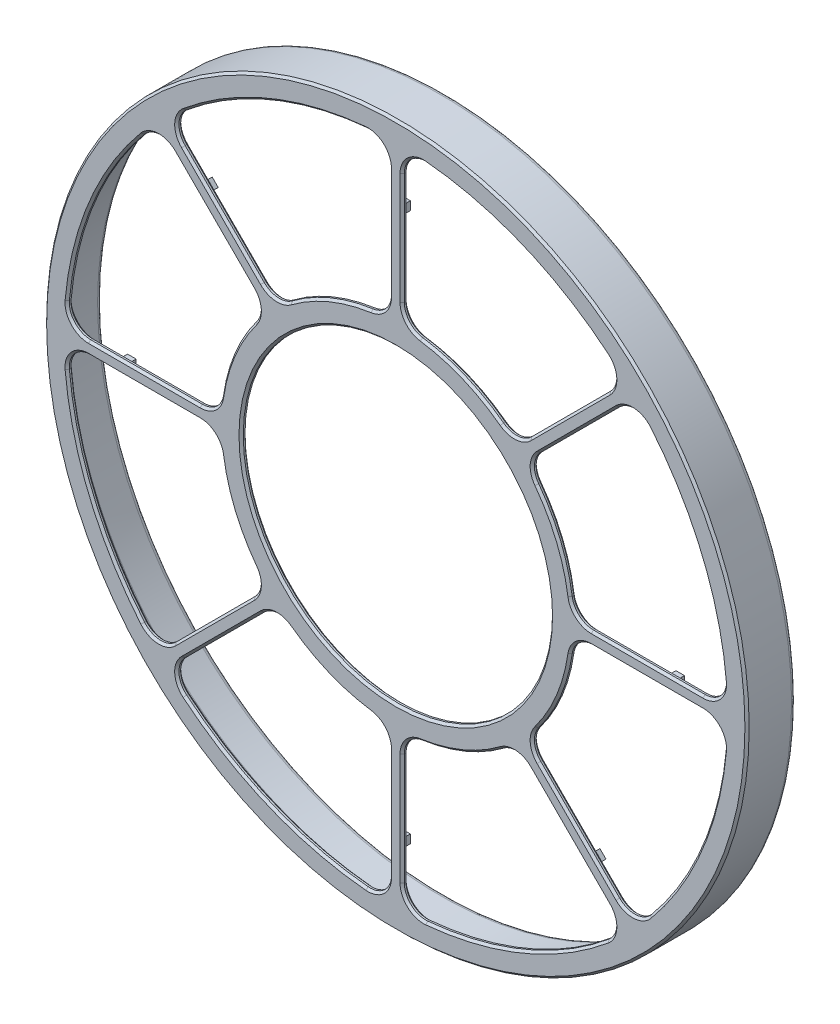
SolidWorks part; units mm, degrees
ref_plane "Front" through (0, 0, 0) normal (0, 0, 1) x (1, 0, 0)
ref_plane "Top" through (0, 0, 0) normal (0, 1, 0) x (1, 0, 0)
ref_plane "Right" through (0, 0, 0) normal (1, 0, 0) x (0, 0, -1)
other "Configuration Table"
sketch "Sketch1" plane through (0, 0, 0) normal (0, 0, 1) x (1, 0, 0)
  line L0 (0, 0) -> (0, 97.79) construction
  line L1 (38.2313, 35.5372) -> (70.4819, 67.7878)
  line L3 (-1.905, 52.1622) -> (-1.905, 97.7714)
  line L5 (1.905, 52.1622) -> (1.905, 97.7714)
  line L6 (35.5372, 38.2313) -> (67.7878, 70.4819)
  line L7 (52.1622, -1.905) -> (97.7714, -1.905)
  line L8 (52.1622, 1.905) -> (97.7714, 1.905)
  line L9 (35.5372, -38.2313) -> (67.7878, -70.4819)
  line L10 (38.2313, -35.5372) -> (70.4819, -67.7878)
  line L11 (-1.905, -52.1622) -> (-1.905, -97.7714)
  line L12 (1.905, -52.1622) -> (1.905, -97.7714)
  line L13 (-38.2313, -35.5372) -> (-70.4819, -67.7878)
  line L14 (-35.5372, -38.2313) -> (-67.7878, -70.4819)
  line L15 (-52.1622, 1.905) -> (-97.7714, 1.905)
  line L16 (-52.1622, -1.905) -> (-97.7714, -1.905)
  line L17 (-35.5372, 38.2313) -> (-67.7878, 70.4819)
  line L18 (-38.2313, 35.5372) -> (-70.4819, 67.7878)
  circle A0 centre (0, 0) radius 45.847
  circle A1 centre (0, 0) radius 104.14
  circle A2 centre (0, 0) radius 97.79
  circle A3 centre (0, 0) radius 52.197
  point P16 (0, 48.0198)
  point P47 (0, 0)
  dimension "D1" = 91.694
  dimension "D2" = 208.28
  dimension "D7" = 3.81
  dimension "D8" = 1.905
  dimension "D3" = 6.35
  dimension "D4" = 6.35
  dimension "D9" = 8
extrude "Boss-Extrude5" add sketch "Sketch1" along normal blind 1.778
fillet "Fillet1" radius 6.35 32 edges at (35.5372, 38.2313, 0.889) (67.7878, 70.4819, 0.889) (1.905, 97.7714, 0.889) (97.7714, 1.905, 0.889) (70.4819, 67.7878, 0.889) (38.2313, 35.5372, 0.889) (52.1622, 1.905, 0.889) (97.7714, -1.905, 0.889) (52.1622, -1.905, 0.889) (38.2313, -35.5372, 0.889) (70.4819, -67.7878, 0.889) (1.905, -52.1622, 0.889) (1.905, -97.7714, 0.889) (67.7878, -70.4819, 0.889) (35.5372, -38.2313, 0.889) (-1.905, -52.1622, 0.889) (-1.905, -97.7714, 0.889) (-35.5372, -38.2313, 0.889) (-67.7878, -70.4819, 0.889) (-38.2313, -35.5372, 0.889) (-70.4819, -67.7878, 0.889) (-52.1622, -1.905, 0.889) (-97.7714, -1.905, 0.889) (-97.7714, 1.905, 0.889) (-52.1622, 1.905, 0.889) (-70.4819, 67.7878, 0.889) (-38.2313, 35.5372, 0.889) (-1.905, 97.7714, 0.889) (-67.7878, 70.4819, 0.889) (1.905, 52.1622, 0.889) (-35.5372, 38.2313, 0.889) (-1.905, 52.1622, 0.889)
sketch "Sketch2" plane through (0, 0, 0) normal (0, 0, -1) x (-1, 0, 0)
  circle A0 centre (0, 0) radius 104.14
  circle A1 centre (0, 0) radius 101.6
  circle A3 centre (0, 0) radius 104.14 construction
  dimension "D1" = 2.54
extrude "Boss-Extrude6" add sketch "Sketch2" along normal blind 12.7 contours A0 | A1
fillet "Fillet2" radius 2.54 1 edges at (-101.6, 0, 0)
chamfer "Chamfer2" distance 0.635 angle 45 131 edges at (-40.4884, -35.597, 1.778) (-40.4884, -35.597, 0) (-54.0366, -51.3426, 1.778) (-54.0366, -51.3426, 0) (-70.5179, -64.9002, 1.778) (-70.5179, -64.9002, 0) (-90.3462, -37.4226, 1.778) (-90.3462, -37.4226, 0) (-95.755, -3.9723, 1.778) (-95.755, -3.9723, 0) (-74.5144, -1.905, 0) (-74.5144, -1.905, 1.778) (-53.8006, -3.4588, 1.778) (-53.8006, -3.4588, 0) (-48.2237, -19.9749, 1.778) (-48.2237, -19.9749, 0) (-3.4588, -53.8006, 1.778) (-3.4588, -53.8006, 0) (-1.905, -74.5144, 1.778) (-1.905, -74.5144, 0) (-3.9723, -95.755, 1.778) (-3.9723, -95.755, 0) (-37.4226, -90.3462, 1.778) (-37.4226, -90.3462, 0) (-64.9002, -70.5179, 1.778) (-64.9002, -70.5179, 0) (-51.3426, -54.0366, 0) (-51.3426, -54.0366, 1.778) (-35.597, -40.4884, 1.778) (-35.597, -40.4884, 0) (-19.9749, -48.2237, 1.778) (-19.9749, -48.2237, 0) (35.597, -40.4884, 1.778) (35.597, -40.4884, 0) (51.3426, -54.0366, 0) (51.3426, -54.0366, 1.778) (64.9002, -70.5179, 1.778) (64.9002, -70.5179, 0) (37.4226, -90.3462, 1.778) (37.4226, -90.3462, 0) (3.9723, -95.755, 1.778) (3.9723, -95.755, 0) (1.905, -74.5144, 0) (1.905, -74.5144, 1.778) (3.4588, -53.8006, 1.778) (3.4588, -53.8006, 0) (19.9749, -48.2237, 1.778) (19.9749, -48.2237, 0) (53.8006, -3.4588, 1.778) (53.8006, -3.4588, 0) (74.5144, -1.905, 0) (74.5144, -1.905, 1.778) (95.755, -3.9723, 1.778) (95.755, -3.9723, 0) (90.3462, -37.4226, 1.778) (90.3462, -37.4226, 0) (70.5179, -64.9002, 1.778) (70.5179, -64.9002, 0) (54.0366, -51.3426, 0) (54.0366, -51.3426, 1.778) (40.4884, -35.597, 1.778) (40.4884, -35.597, 0) (48.2237, -19.9749, 1.778) (48.2237, -19.9749, 0) (40.4884, 35.597, 1.778) (40.4884, 35.597, 0) (54.0366, 51.3426, 0) (54.0366, 51.3426, 1.778) (70.5179, 64.9002, 1.778) (70.5179, 64.9002, 0) (90.3462, 37.4226, 1.778) (90.3462, 37.4226, 0) (95.755, 3.9723, 1.778) (95.755, 3.9723, 0) (74.5144, 1.905, 1.778) (74.5144, 1.905, 0) (53.8006, 3.4588, 1.778) (53.8006, 3.4588, 0) (48.2237, 19.9749, 1.778) (48.2237, 19.9749, 0) (3.4588, 53.8006, 1.778) (3.4588, 53.8006, 0) (1.905, 74.5144, 0) (1.905, 74.5144, 1.778) (3.9723, 95.755, 1.778) (3.9723, 95.755, 0) (37.4226, 90.3462, 1.778) (37.4226, 90.3462, 0) (64.9002, 70.5179, 1.778) (64.9002, 70.5179, 0) (51.3426, 54.0366, 0) (51.3426, 54.0366, 1.778) (35.597, 40.4884, 1.778) (35.597, 40.4884, 0) (19.9749, 48.2237, 1.778) (19.9749, 48.2237, 0) (-19.9749, 48.2237, 1.778) (-19.9749, 48.2237, 0) (-35.597, 40.4884, 1.778) (-35.597, 40.4884, 0) (-51.3426, 54.0366, 0) (-51.3426, 54.0366, 1.778) (-64.9002, 70.5179, 1.778) (-64.9002, 70.5179, 0) (-37.4226, 90.3462, 1.778) (-37.4226, 90.3462, 0) (-3.9723, 95.755, 1.778) (-3.9723, 95.755, 0) (-1.905, 74.5144, 0) (-1.905, 74.5144, 1.778) (-53.8006, 3.4588, 1.778) (-53.8006, 3.4588, 0) (-74.5144, 1.905, 0) (-74.5144, 1.905, 1.778) (-95.755, 3.9723, 1.778) (-95.755, 3.9723, 0) (-90.3462, 37.4226, 1.778) (-90.3462, 37.4226, 0) (-70.5179, 64.9002, 1.778) (-70.5179, 64.9002, 0) (-54.0366, 51.3426, 1.778) (-54.0366, 51.3426, 0) (-40.4884, 35.597, 1.778) (-40.4884, 35.597, 0) (-48.2237, 19.9749, 1.778) (-48.2237, 19.9749, 0) (45.847, 0, 1.778) (45.847, 0, 0) (104.14, 0, 1.778) (-3.4588, 53.8006, 1.778) (-3.4588, 53.8006, 0)
sketch "Sketch4" plane through (0, 0, 0) normal (0, 0, -1) x (-1, 0, 0)
  line L0 (-1.27, 91.0666) -> (-1.27, 57.9621) construction
  line L1 (-1.27, 82.55) -> (1.27, 82.55)
  line L2 (-1.27, 82.55) -> (-1.27, 80.01)
  line L3 (-1.27, 80.01) -> (1.27, 80.01)
  line L4 (1.27, 82.55) -> (1.27, 80.01)
  line L5 (1.27, 57.9621) -> (1.27, 91.0666) construction
  line L6 (57.4736, 59.2697) -> (55.6776, 57.4736)
  line L7 (57.4736, 59.2697) -> (59.2697, 57.4736)
  line L8 (59.2697, 57.4736) -> (57.4736, 55.6776)
  line L9 (55.6776, 57.4736) -> (57.4736, 55.6776)
  line L10 (82.55, 1.27) -> (80.01, 1.27)
  line L11 (82.55, 1.27) -> (82.55, -1.27)
  line L12 (82.55, -1.27) -> (80.01, -1.27)
  line L13 (80.01, 1.27) -> (80.01, -1.27)
  line L14 (59.2697, -57.4736) -> (57.4736, -55.6776)
  line L15 (59.2697, -57.4736) -> (57.4736, -59.2697)
  line L16 (57.4736, -59.2697) -> (55.6776, -57.4736)
  line L17 (57.4736, -55.6776) -> (55.6776, -57.4736)
  line L18 (1.27, -82.55) -> (1.27, -80.01)
  line L19 (1.27, -82.55) -> (-1.27, -82.55)
  line L20 (-1.27, -82.55) -> (-1.27, -80.01)
  line L21 (1.27, -80.01) -> (-1.27, -80.01)
  line L22 (-57.4736, -59.2697) -> (-55.6776, -57.4736)
  line L23 (-57.4736, -59.2697) -> (-59.2697, -57.4736)
  line L24 (-59.2697, -57.4736) -> (-57.4736, -55.6776)
  line L25 (-55.6776, -57.4736) -> (-57.4736, -55.6776)
  line L26 (-82.55, -1.27) -> (-80.01, -1.27)
  line L27 (-82.55, -1.27) -> (-82.55, 1.27)
  line L28 (-82.55, 1.27) -> (-80.01, 1.27)
  line L29 (-80.01, -1.27) -> (-80.01, 1.27)
  line L30 (-59.2697, 57.4736) -> (-57.4736, 55.6776)
  line L31 (-59.2697, 57.4736) -> (-57.4736, 59.2697)
  line L32 (-57.4736, 59.2697) -> (-55.6776, 57.4736)
  line L33 (-57.4736, 55.6776) -> (-55.6776, 57.4736)
  circle A2 centre (0, 0) radius 104.14 construction
  point P3 (0, 82.55)
  point P43 (0, 0)
  dimension "D1" = 82.55
  dimension "D3" = 8
  dimension "D2" = 2.54
extrude "Boss-Extrude7" add sketch "Sketch4" along normal blind 1.27 contours L30 L33 L32 L31 | L2 L1 L4 L3 | L6 L9 L8 L7 | L10 L13 L12 L11 | L14 L17 L16 L15 | L18 L21 L20 L19 | L22 L25 L24 L23 | L26 L29 L28 L27
fillet "Fillet3" radius 1.27 2 edges at (-101.6, 0, -12.7) (-104.14, 0, -12.7)
